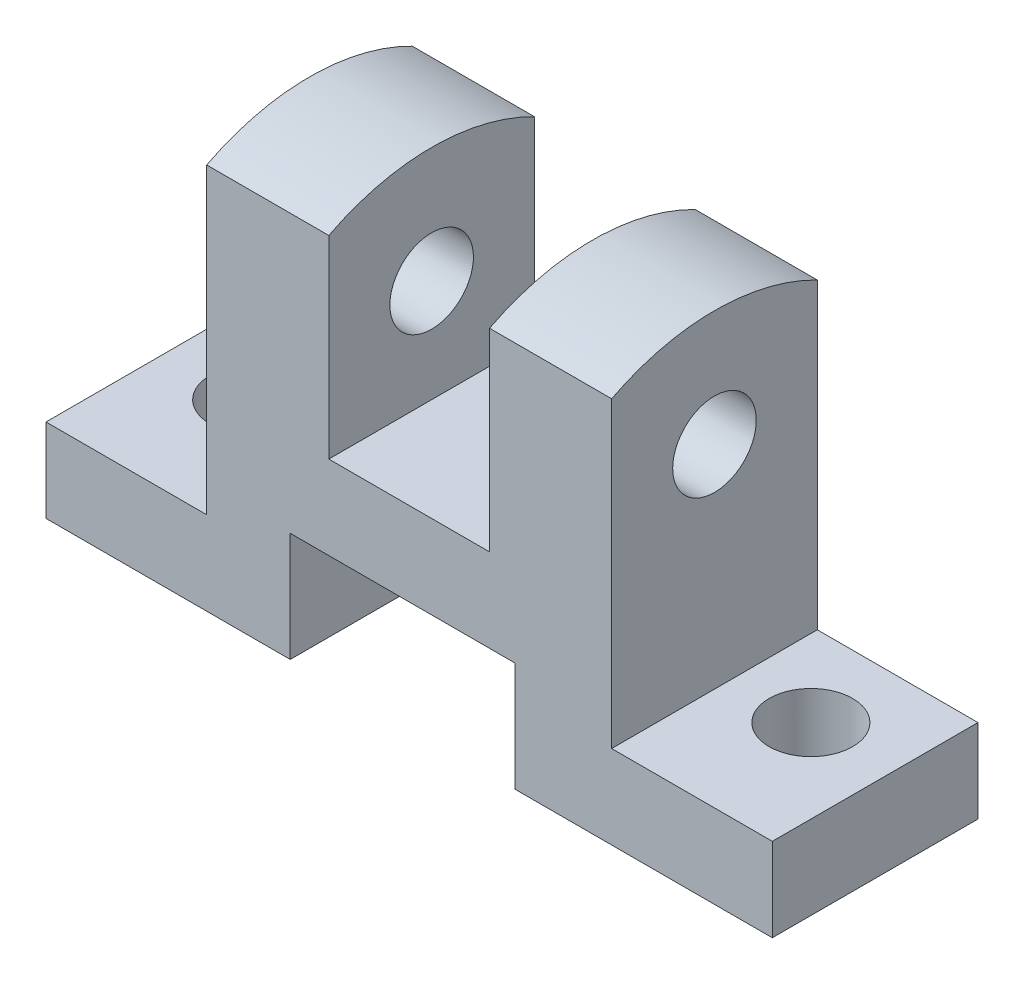
SolidWorks part; units mm, degrees
ref_plane "Front Plane" through (0, 0, 0) normal (0, 0, 1) x (1, 0, 0)
ref_plane "Top Plane" through (0, 0, 0) normal (0, 1, 0) x (1, 0, 0)
ref_plane "Right Plane" through (0, 0, 0) normal (1, 0, 0) x (0, 0, -1)
sketch "Sketch1" plane through (0, 0, 0) normal (0, 0, 1) x (1, 0, 0)
  line L0 (-64.8772, -12.1179) -> (-64.8772, -25.1179)
  line L1 (-64.8772, -25.1179) -> (-26.8772, -25.1179)
  line L2 (-26.8772, -25.1179) -> (-26.8772, -8.1179)
  line L3 (-26.8772, -8.1179) -> (8.1228, -8.1179)
  line L4 (8.1228, -8.1179) -> (8.1228, -25.1179)
  line L5 (8.1228, -25.1179) -> (48.1228, -25.1179)
  line L6 (48.1228, -12.1179) -> (23.1228, -12.1179)
  line L7 (23.1228, -12.1179) -> (23.1228, 38.8821)
  line L8 (23.1228, 38.8821) -> (4.1228, 38.8821)
  line L9 (4.1228, 38.8821) -> (4.1228, 4.8821)
  line L10 (4.1228, 4.8821) -> (-20.8772, 4.8821)
  line L11 (-20.8772, 4.8821) -> (-20.8772, 38.8821)
  line L12 (-20.8772, 38.8821) -> (-39.8772, 38.8821)
  line L13 (-39.8772, 38.8821) -> (-39.8772, -12.1179)
  line L14 (-39.8772, -12.1179) -> (-64.8772, -12.1179)
  line L15 (48.1228, -25.1179) -> (48.1228, -12.1179)
  dimension "D1" = 19
  dimension "D2" = 19
  dimension "D3" = 25
  dimension "D4" = 25
  dimension "D5" = 25
  dimension "D6" = 35
  dimension "D7" = 40
  dimension "D8" = 13
  dimension "D9" = 13
  dimension "D10" = 17
  dimension "D11" = 13
  dimension "D12" = 17
  dimension "D13" = 64
  dimension "D14" = 64
extrude "Boss-Extrude1" add sketch "Sketch1" along normal blind 32
sketch "Sketch2" plane through (0, -12.1179, 0) normal (0, 1, 0) x (1, 0, 0)
  line L0 (48.1228, 0) -> (23.1228, 0) construction
  line L1 (48.1228, -32) -> (48.1228, 0) construction
  line L2 (-8.3772, 0) -> (-8.3772, -32) construction
  line L3 (4.1228, 0) -> (-20.8772, 0) construction
  line L4 (4.1228, -32) -> (-20.8772, -32) construction
  circle A0 centre (35.1228, -13) radius 6.5
  circle A1 centre (-51.8772, -13) radius 6.5
  dimension "D1" = 13
  dimension "D4" = 56.5
  dimension "D2" = 13
  dimension "D3" = 13
extrude "Cut-Extrude1" cut sketch "Sketch2" against normal blind 32 contours A0 | A1
sketch "Sketch3" plane through (-39.8772, 0, 0) normal (-1, 0, 0) x (0, 0, 1)
  line L0 (32, -25.1179) -> (0, -25.1179) construction
  line L1 (32, 38.8821) -> (32, -12.1179) construction
  circle A0 centre (16, 20.8821) radius 6.5
  point P6 (-49.4225, 40.1587)
  dimension "D1" = 13
  dimension "D2" = 46
  dimension "D3" = 16
extrude "Cut-Extrude2" cut sketch "Sketch3" against normal blind 76 contours A0
sketch "Sketch4" plane through (23.1228, 0, 0) normal (1, 0, 0) x (0, 0, -1)
  line L0 (-32, -25.1179) -> (-32, -12.1179) construction
  line L1 (-32, 38.8821) -> (0, 38.8821) construction
  line L2 (-32, 38.8821) -> (0, 38.8821)
  line L3 (0, 35.0108) -> (0, 38.8821)
  line L4 (0, -12.1179) -> (0, 38.8821) construction
  line L5 (-32, 38.8821) -> (-32, 35.0108)
  line L6 (-7.9018, 28.8821) -> (-7.9018, 28.8821)
  line L7 (-24.0982, 28.8821) -> (-7.9018, 28.8821)
  line L8 (-24.0982, 28.8821) -> (-24.0982, 28.8821)
  arc A0 (0, 35.0108) -> (-32, 35.0108) centre (-16, 3.8821) ccw
  dimension "D1" = 70
  dimension "D2" = 16
  dimension "D3" = 35
  dimension "D4" = 10
extrude "Cut-Extrude5" cut sketch "Sketch4" against normal through all and the other way through all contours A0 L2 L3 | A0 L1 L2 region at (23.1228, 37.7326, 3.9544) region at (23.1228, 37.7326, 28.0456)
